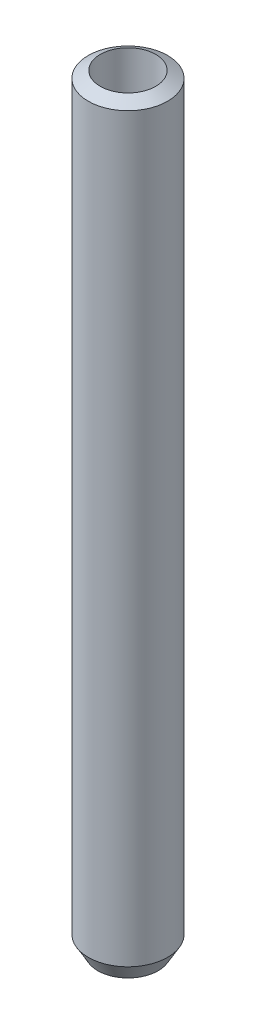
SolidWorks part; units mm, degrees
ref_plane "Front Plane" through (0, 0, 0) normal (0, 0, 1) x (1, 0, 0)
ref_plane "Top Plane" through (0, 0, 0) normal (0, 1, 0) x (1, 0, 0)
ref_plane "Right Plane" through (0, 0, 0) normal (1, 0, 0) x (0, 0, -1)
sketch "Sketch1" plane through (0, 0, 0) normal (0, 1, 0) x (1, 0, 0)
  circle A0 centre (0, 0) radius 10
  dimension "SHAFT_OD" = 20
extrude "Boss-Extrude1" add sketch "Sketch1" along normal blind 193.38
sketch "Sketch2" plane through (0, 0, 0) normal (0, 1, 0) x (1, 0, 0)
  circle A0 centre (0, 0) radius 6.9849
  dimension "BORE_D" = 13.9697
extrude "Cut-Extrude1" cut sketch "Sketch2" along normal through all
chamfer "Chamfer1" distance 2.3831 angle 60 2 edges at (0, 193.38, 10) (0, 0, 10) first distance on face at (0, 193.38, 10) first distance on face at (0, 0, 6.9849)
